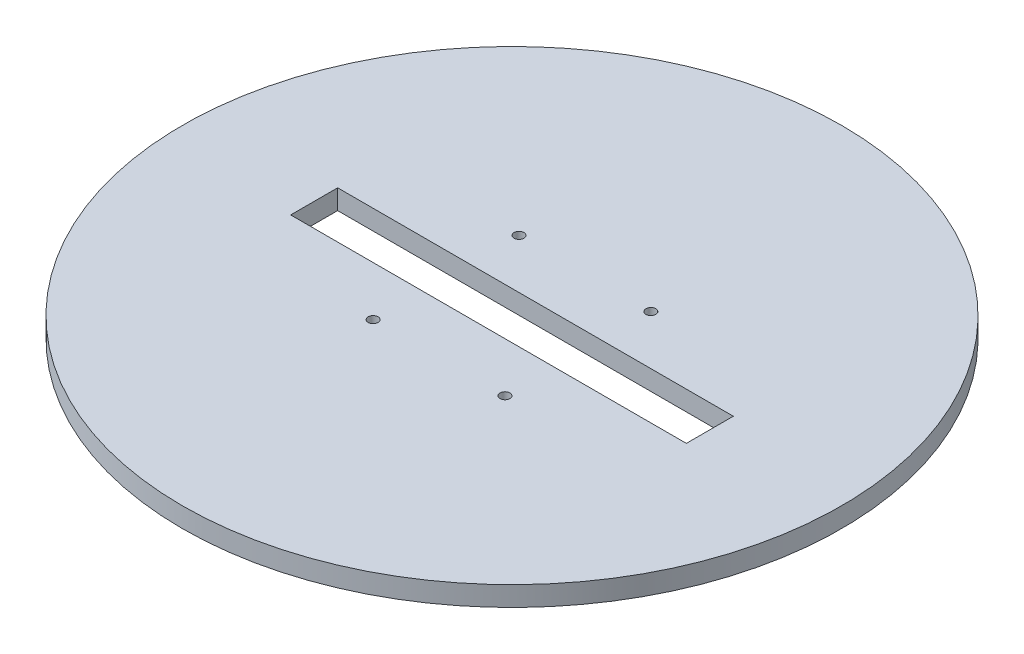
SolidWorks part; units mm, degrees
note: '?' marks a value the reader was unsure of.
ref_plane "Front Plane" through (0, 0, 0) normal (0, 0, 1) x (1, 0, 0)
ref_plane "Top Plane" through (0, 0, 0) normal (0, 1, 0) x (1, 0, 0)
ref_plane "Right Plane" through (0, 0, 0) normal (1, 0, 0) x (0, 0, -1)
sketch "Sketch1" plane through (0, 0, 0) normal (0, 1, 0) x (1, 0, 0)
  line L1 (-60, -7.125) -> (60, -7.125)
  line L2 (-60, -7.125) -> (-60, 7.125)
  line L3 (-60, 7.125) -> (60, 7.125)
  line L4 (60, -7.125) -> (60, 7.125)
  line L5 (-60, -7.125) -> (60, 7.125) construction
  line L6 (-60, 7.125) -> (60, -7.125) construction
  circle A0 centre (0, 0) radius 99.95
extrude "Boss-Extrude1" add sketch "Sketch1" along normal blind 6 contours A0 L4 L1 L2 L3
sketch "Sketch2" plane through (0, 6, 0) normal (0, 1, 0) x (1, 0, 0)
  line L0 (0, 70) -> (0, 80)
  line L1 (1.2217, 69.9893) -> (1.3962, 79.9878)
  line L2 (2.443, 69.9574) -> (2.792, 79.9513)
  line L3 (3.6635, 69.9041) -> (4.1869, 79.8904)
  line L4 (4.883, 69.8295) -> (5.5805, 79.8051)
  line L5 (6.1009, 69.7336) -> (6.9725, 79.6956)
  line L6 (7.317, 69.6165) -> (8.3623, 79.5618)
  line L7 (8.5309, 69.4782) -> (9.7495, 79.4037)
  line L8 (9.7421, 69.3188) -> (11.1338, 79.2214)
  line L9 (10.9504, 69.1382) -> (12.5148, 79.0151)
  line L10 (12.1554, 68.9365) -> (13.8919, 78.7846)
  line L11 (13.3566, 68.7139) -> (15.2647, 78.5302)
  line L12 (14.5538, 68.4703) -> (16.6329, 78.2518)
  line L13 (15.7466, 68.2059) -> (17.9961, 77.9496)
  line L14 (16.9345, 67.9207) -> (19.3538, 77.6237)
  line L15 (18.1173, 67.6148) -> (20.7055, 77.2741)
  line L16 (19.2946, 67.2883) -> (22.051, 76.9009)
  line L17 (20.466, 66.9413) -> (23.3897, 76.5044)
  line L18 (21.6312, 66.574) -> (24.7214, 76.0845)
  line L19 (22.7898, 66.1863) -> (26.0455, 75.6415)
  line L20 (23.9414, 65.7785) -> (27.3616, 75.1754)
  line L21 (25.0858, 65.3506) -> (28.6694, 74.6864)
  line L22 (26.2225, 64.9029) -> (29.9685, 74.1747)
  line L23 (27.3512, 64.4353) -> (31.2585, 73.6404)
  line L24 (28.4716, 63.9482) -> (32.5389, 73.0836)
  line L25 (29.5833, 63.4415) -> (33.8095, 72.5046)
  line L26 (30.686, 62.9156) -> (35.0697, 71.9035)
  line L27 (31.7793, 62.3705) -> (36.3192, 71.2805)
  line L28 (32.863, 61.8063) -> (37.5577, 70.6358)
  line L29 (33.9367, 61.2234) -> (38.7848, 69.9696)
  line L30 (35, 60.6218) -> (40, 69.282)
  line L31 (36.0527, 60.0017) -> (41.203, 68.5734)
  line L32 (37.0943, 59.3634) -> (42.3935, 67.8438)
  line L33 (38.1247, 58.7069) -> (43.5711, 67.0936)
  line L34 (39.1435, 58.0326) -> (44.7354, 66.323)
  line L35 (40.1504, 57.3406) -> (45.8861, 65.5322)
  line L36 (41.145, 56.6312) -> (47.0228, 64.7214)
  line L37 (42.1271, 55.9045) -> (48.1452, 63.8908)
  line L38 (43.0963, 55.1608) -> (49.2529, 63.0409)
  line L39 (44.0524, 54.4002) -> (50.3456, 62.1717)
  line L40 (44.9951, 53.6231) -> (51.423, 61.2836)
  line L41 (45.9241, 52.8297) -> (52.4847, 60.3768)
  line L42 (46.8391, 52.0201) -> (53.5304, 59.4516)
  line L43 (47.7399, 51.1948) -> (54.5599, 58.5083)
  line L44 (48.6261, 50.3538) -> (55.5727, 57.5472)
  line L45 (49.4975, 49.4975) -> (56.5685, 56.5685)
  line L46 (50.3538, 48.6261) -> (57.5472, 55.5727)
  line L47 (51.1948, 47.7399) -> (58.5083, 54.5599)
  line L48 (52.0201, 46.8391) -> (59.4516, 53.5304)
  line L49 (52.8297, 45.9241) -> (60.3768, 52.4847)
  line L50 (53.6231, 44.9951) -> (61.2836, 51.423)
  line L51 (54.4002, 44.0524) -> (62.1717, 50.3456)
  line L52 (55.1608, 43.0963) -> (63.0409, 49.2529)
  line L53 (55.9045, 42.1271) -> (63.8908, 48.1452)
  line L54 (56.6312, 41.145) -> (64.7214, 47.0228)
  line L55 (57.3406, 40.1504) -> (65.5322, 45.8861)
  line L56 (58.0326, 39.1435) -> (66.323, 44.7354)
  line L57 (58.7069, 38.1247) -> (67.0936, 43.5711)
  line L58 (59.3634, 37.0943) -> (67.8438, 42.3935)
  line L59 (60.0017, 36.0527) -> (68.5734, 41.203)
  line L60 (60.6218, 35) -> (69.282, 40)
  line L61 (61.2234, 33.9367) -> (69.9696, 38.7848)
  line L62 (61.8063, 32.863) -> (70.6358, 37.5577)
  line L63 (62.3705, 31.7793) -> (71.2805, 36.3192)
  line L64 (62.9156, 30.686) -> (71.9035, 35.0697)
  line L65 (63.4415, 29.5833) -> (72.5046, 33.8095)
  line L66 (63.9482, 28.4716) -> (73.0836, 32.5389)
  line L67 (64.4353, 27.3512) -> (73.6404, 31.2585)
  line L68 (64.9029, 26.2225) -> (74.1747, 29.9685)
  line L69 (65.3506, 25.0858) -> (74.6864, 28.6694)
  line L70 (65.7785, 23.9414) -> (75.1754, 27.3616)
  line L71 (66.1863, 22.7898) -> (75.6415, 26.0455)
  line L72 (66.574, 21.6312) -> (76.0845, 24.7214)
  line L73 (66.9413, 20.466) -> (76.5044, 23.3897)
  line L74 (67.2883, 19.2946) -> (76.9009, 22.051)
  line L75 (67.6148, 18.1173) -> (77.2741, 20.7055)
  line L76 (67.9207, 16.9345) -> (77.6237, 19.3538)
  line L77 (68.2059, 15.7466) -> (77.9496, 17.9961)
  line L78 (68.4703, 14.5538) -> (78.2518, 16.6329)
  line L79 (68.7139, 13.3566) -> (78.5302, 15.2647)
  line L80 (68.9365, 12.1554) -> (78.7846, 13.8919)
  line L81 (69.1382, 10.9504) -> (79.0151, 12.5148)
  line L82 (69.3188, 9.7421) -> (79.2214, 11.1338)
  line L83 (69.4782, 8.5309) -> (79.4037, 9.7495)
  line L84 (69.6165, 7.317) -> (79.5618, 8.3623)
  line L85 (69.7336, 6.1009) -> (79.6956, 6.9725)
  line L86 (69.8295, 4.883) -> (79.8051, 5.5805)
  line L87 (69.9041, 3.6635) -> (79.8904, 4.1869)
  line L88 (69.9574, 2.443) -> (79.9513, 2.792)
  line L89 (69.9893, 1.2217) -> (79.9878, 1.3962)
  line L90 (70, 0) -> (80, 0)
  line L91 (69.9893, -1.2217) -> (79.9878, -1.3962)
  line L92 (69.9574, -2.443) -> (79.9513, -2.792)
  line L93 (69.9041, -3.6635) -> (79.8904, -4.1869)
  line L94 (69.8295, -4.883) -> (79.8051, -5.5805)
  line L95 (69.7336, -6.1009) -> (79.6956, -6.9725)
  line L96 (69.6165, -7.317) -> (79.5618, -8.3623)
  line L97 (69.4782, -8.5309) -> (79.4037, -9.7495)
  line L98 (69.3188, -9.7421) -> (79.2214, -11.1338)
  line L99 (69.1382, -10.9504) -> (79.0151, -12.5148)
  line L100 (68.9365, -12.1554) -> (78.7846, -13.8919)
  line L101 (68.7139, -13.3566) -> (78.5302, -15.2647)
  line L102 (68.4703, -14.5538) -> (78.2518, -16.6329)
  line L103 (68.2059, -15.7466) -> (77.9496, -17.9961)
  line L104 (67.9207, -16.9345) -> (77.6237, -19.3538)
  line L105 (67.6148, -18.1173) -> (77.2741, -20.7055)
  line L106 (67.2883, -19.2946) -> (76.9009, -22.051)
  line L107 (66.9413, -20.466) -> (76.5044, -23.3897)
  line L108 (66.574, -21.6312) -> (76.0845, -24.7214)
  line L109 (66.1863, -22.7898) -> (75.6415, -26.0455)
  line L110 (65.7785, -23.9414) -> (75.1754, -27.3616)
  line L111 (65.3506, -25.0858) -> (74.6864, -28.6694)
  line L112 (64.9029, -26.2225) -> (74.1747, -29.9685)
  line L113 (64.4353, -27.3512) -> (73.6404, -31.2585)
  line L114 (63.9482, -28.4716) -> (73.0836, -32.5389)
  line L115 (63.4415, -29.5833) -> (72.5046, -33.8095)
  line L116 (62.9156, -30.686) -> (71.9035, -35.0697)
  line L117 (62.3705, -31.7793) -> (71.2805, -36.3192)
  line L118 (61.8063, -32.863) -> (70.6358, -37.5577)
  line L119 (61.2234, -33.9367) -> (69.9696, -38.7848)
  line L120 (60.6218, -35) -> (69.282, -40)
  line L121 (60.0017, -36.0527) -> (68.5734, -41.203)
  line L122 (59.3634, -37.0943) -> (67.8438, -42.3935)
  line L123 (58.7069, -38.1247) -> (67.0936, -43.5711)
  line L124 (58.0326, -39.1435) -> (66.323, -44.7354)
  line L125 (57.3406, -40.1504) -> (65.5322, -45.8861)
  line L126 (56.6312, -41.145) -> (64.7214, -47.0228)
  line L127 (55.9045, -42.1271) -> (63.8908, -48.1452)
  line L128 (55.1608, -43.0963) -> (63.0409, -49.2529)
  line L129 (54.4002, -44.0524) -> (62.1717, -50.3456)
  line L130 (53.6231, -44.9951) -> (61.2836, -51.423)
  line L131 (52.8297, -45.9241) -> (60.3768, -52.4847)
  line L132 (52.0201, -46.8391) -> (59.4516, -53.5304)
  line L133 (51.1948, -47.7399) -> (58.5083, -54.5599)
  line L134 (50.3538, -48.6261) -> (57.5472, -55.5727)
  line L135 (49.4975, -49.4975) -> (56.5685, -56.5685)
  line L136 (48.6261, -50.3538) -> (55.5727, -57.5472)
  line L137 (47.7399, -51.1948) -> (54.5599, -58.5083)
  line L138 (46.8391, -52.0201) -> (53.5304, -59.4516)
  line L139 (45.9241, -52.8297) -> (52.4847, -60.3768)
  line L140 (44.9951, -53.6231) -> (51.423, -61.2836)
  line L141 (44.0524, -54.4002) -> (50.3456, -62.1717)
  line L142 (43.0963, -55.1608) -> (49.2529, -63.0409)
  line L143 (42.1271, -55.9045) -> (48.1452, -63.8908)
  line L144 (41.145, -56.6312) -> (47.0228, -64.7214)
  line L145 (40.1504, -57.3406) -> (45.8861, -65.5322)
  line L146 (39.1435, -58.0326) -> (44.7354, -66.323)
  line L147 (38.1247, -58.7069) -> (43.5711, -67.0936)
  line L148 (37.0943, -59.3634) -> (42.3935, -67.8438)
  line L149 (36.0527, -60.0017) -> (41.203, -68.5734)
  line L150 (35, -60.6218) -> (40, -69.282)
  line L151 (33.9367, -61.2234) -> (38.7848, -69.9696)
  line L152 (32.863, -61.8063) -> (37.5577, -70.6358)
  line L153 (31.7793, -62.3705) -> (36.3192, -71.2805)
  line L154 (30.686, -62.9156) -> (35.0697, -71.9035)
  line L155 (29.5833, -63.4415) -> (33.8095, -72.5046)
  line L156 (28.4716, -63.9482) -> (32.5389, -73.0836)
  line L157 (27.3512, -64.4353) -> (31.2585, -73.6404)
  line L158 (26.2225, -64.9029) -> (29.9685, -74.1747)
  line L159 (25.0858, -65.3506) -> (28.6694, -74.6864)
  line L160 (23.9414, -65.7785) -> (27.3616, -75.1754)
  line L161 (22.7898, -66.1863) -> (26.0455, -75.6415)
  line L162 (21.6312, -66.574) -> (24.7214, -76.0845)
  line L163 (20.466, -66.9413) -> (23.3897, -76.5044)
  line L164 (19.2946, -67.2883) -> (22.051, -76.9009)
  line L165 (18.1173, -67.6148) -> (20.7055, -77.2741)
  line L166 (16.9345, -67.9207) -> (19.3538, -77.6237)
  line L167 (15.7466, -68.2059) -> (17.9961, -77.9496)
  line L168 (14.5538, -68.4703) -> (16.6329, -78.2518)
  line L169 (13.3566, -68.7139) -> (15.2647, -78.5302)
  line L170 (12.1554, -68.9365) -> (13.8919, -78.7846)
  line L171 (10.9504, -69.1382) -> (12.5148, -79.0151)
  line L172 (9.7421, -69.3188) -> (11.1338, -79.2214)
  line L173 (8.5309, -69.4782) -> (9.7495, -79.4037)
  line L174 (7.317, -69.6165) -> (8.3623, -79.5618)
  line L175 (6.1009, -69.7336) -> (6.9725, -79.6956)
  line L176 (4.883, -69.8295) -> (5.5805, -79.8051)
  line L177 (3.6635, -69.9041) -> (4.1869, -79.8904)
  line L178 (2.443, -69.9574) -> (2.792, -79.9513)
  line L179 (1.2217, -69.9893) -> (1.3962, -79.9878)
  line L180 (0, -70) -> (0, -80)
  line L181 (-1.2217, -69.9893) -> (-1.3962, -79.9878)
  line L182 (-2.443, -69.9574) -> (-2.792, -79.9513)
  line L183 (-3.6635, -69.9041) -> (-4.1869, -79.8904)
  line L184 (-4.883, -69.8295) -> (-5.5805, -79.8051)
  line L185 (-6.1009, -69.7336) -> (-6.9725, -79.6956)
  line L186 (-7.317, -69.6165) -> (-8.3623, -79.5618)
  line L187 (-8.5309, -69.4782) -> (-9.7495, -79.4037)
  line L188 (-9.7421, -69.3188) -> (-11.1338, -79.2214)
  line L189 (-10.9504, -69.1382) -> (-12.5148, -79.0151)
  line L190 (-12.1554, -68.9365) -> (-13.8919, -78.7846)
  line L191 (-13.3566, -68.7139) -> (-15.2647, -78.5302)
  line L192 (-14.5538, -68.4703) -> (-16.6329, -78.2518)
  line L193 (-15.7466, -68.2059) -> (-17.9961, -77.9496)
  line L194 (-16.9345, -67.9207) -> (-19.3538, -77.6237)
  line L195 (-18.1173, -67.6148) -> (-20.7055, -77.2741)
  line L196 (-19.2946, -67.2883) -> (-22.051, -76.9009)
  line L197 (-20.466, -66.9413) -> (-23.3897, -76.5044)
  line L198 (-21.6312, -66.574) -> (-24.7214, -76.0845)
  line L199 (-22.7898, -66.1863) -> (-26.0455, -75.6415)
  line L200 (-23.9414, -65.7785) -> (-27.3616, -75.1754)
  line L201 (-25.0858, -65.3506) -> (-28.6694, -74.6864)
  line L202 (-26.2225, -64.9029) -> (-29.9685, -74.1747)
  line L203 (-27.3512, -64.4353) -> (-31.2585, -73.6404)
  line L204 (-28.4716, -63.9482) -> (-32.5389, -73.0836)
  line L205 (-29.5833, -63.4415) -> (-33.8095, -72.5046)
  line L206 (-30.686, -62.9156) -> (-35.0697, -71.9035)
  line L207 (-31.7793, -62.3705) -> (-36.3192, -71.2805)
  line L208 (-32.863, -61.8063) -> (-37.5577, -70.6358)
  line L209 (-33.9367, -61.2234) -> (-38.7848, -69.9696)
  line L210 (-35, -60.6218) -> (-40, -69.282)
  line L211 (-36.0527, -60.0017) -> (-41.203, -68.5734)
  line L212 (-37.0943, -59.3634) -> (-42.3935, -67.8438)
  line L213 (-38.1247, -58.7069) -> (-43.5711, -67.0936)
  line L214 (-39.1435, -58.0326) -> (-44.7354, -66.323)
  line L215 (-40.1504, -57.3406) -> (-45.8861, -65.5322)
  line L216 (-41.145, -56.6312) -> (-47.0228, -64.7214)
  line L217 (-42.1271, -55.9045) -> (-48.1452, -63.8908)
  line L218 (-43.0963, -55.1608) -> (-49.2529, -63.0409)
  line L219 (-44.0524, -54.4002) -> (-50.3456, -62.1717)
  line L220 (-44.9951, -53.6231) -> (-51.423, -61.2836)
  line L221 (-45.9241, -52.8297) -> (-52.4847, -60.3768)
  line L222 (-46.8391, -52.0201) -> (-53.5304, -59.4516)
  line L223 (-47.7399, -51.1948) -> (-54.5599, -58.5083)
  line L224 (-48.6261, -50.3538) -> (-55.5727, -57.5472)
  line L225 (-49.4975, -49.4975) -> (-56.5685, -56.5685)
  line L226 (-50.3538, -48.6261) -> (-57.5472, -55.5727)
  line L227 (-51.1948, -47.7399) -> (-58.5083, -54.5599)
  line L228 (-52.0201, -46.8391) -> (-59.4516, -53.5304)
  line L229 (-52.8297, -45.9241) -> (-60.3768, -52.4847)
  line L230 (-53.6231, -44.9951) -> (-61.2836, -51.423)
  line L231 (-54.4002, -44.0524) -> (-62.1717, -50.3456)
  line L232 (-55.1608, -43.0963) -> (-63.0409, -49.2529)
  line L233 (-55.9045, -42.1271) -> (-63.8908, -48.1452)
  line L234 (-56.6312, -41.145) -> (-64.7214, -47.0228)
  line L235 (-57.3406, -40.1504) -> (-65.5322, -45.8861)
  line L236 (-58.0326, -39.1435) -> (-66.323, -44.7354)
  line L237 (-58.7069, -38.1247) -> (-67.0936, -43.5711)
  line L238 (-59.3634, -37.0943) -> (-67.8438, -42.3935)
  line L239 (-60.0017, -36.0527) -> (-68.5734, -41.203)
  line L240 (-60.6218, -35) -> (-69.282, -40)
  line L241 (-61.2234, -33.9367) -> (-69.9696, -38.7848)
  line L242 (-61.8063, -32.863) -> (-70.6358, -37.5577)
  line L243 (-62.3705, -31.7793) -> (-71.2805, -36.3192)
  line L244 (-62.9156, -30.686) -> (-71.9035, -35.0697)
  line L245 (-63.4415, -29.5833) -> (-72.5046, -33.8095)
  line L246 (-63.9482, -28.4716) -> (-73.0836, -32.5389)
  line L247 (-64.4353, -27.3512) -> (-73.6404, -31.2585)
  line L248 (-64.9029, -26.2225) -> (-74.1747, -29.9685)
  line L249 (-65.3506, -25.0858) -> (-74.6864, -28.6694)
  line L250 (-65.7785, -23.9414) -> (-75.1754, -27.3616)
  line L251 (-66.1863, -22.7898) -> (-75.6415, -26.0455)
  line L252 (-66.574, -21.6312) -> (-76.0845, -24.7214)
  line L253 (-66.9413, -20.466) -> (-76.5044, -23.3897)
  line L254 (-67.2883, -19.2946) -> (-76.9009, -22.051)
  line L255 (-67.6148, -18.1173) -> (-77.2741, -20.7055)
  line L256 (-67.9207, -16.9345) -> (-77.6237, -19.3538)
  line L257 (-68.2059, -15.7466) -> (-77.9496, -17.9961)
  line L258 (-68.4703, -14.5538) -> (-78.2518, -16.6329)
  line L259 (-68.7139, -13.3566) -> (-78.5302, -15.2647)
  line L260 (-68.9365, -12.1554) -> (-78.7846, -13.8919)
  line L261 (-69.1382, -10.9504) -> (-79.0151, -12.5148)
  line L262 (-69.3188, -9.7421) -> (-79.2214, -11.1338)
  line L263 (-69.4782, -8.5309) -> (-79.4037, -9.7495)
  line L264 (-69.6165, -7.317) -> (-79.5618, -8.3623)
  line L265 (-69.7336, -6.1009) -> (-79.6956, -6.9725)
  line L266 (-69.8295, -4.883) -> (-79.8051, -5.5805)
  line L267 (-69.9041, -3.6635) -> (-79.8904, -4.1869)
  line L268 (-69.9574, -2.443) -> (-79.9513, -2.792)
  line L269 (-69.9893, -1.2217) -> (-79.9878, -1.3962)
  line L270 (-70, 0) -> (-80, 0)
  line L271 (-69.9893, 1.2217) -> (-79.9878, 1.3962)
  line L272 (-69.9574, 2.443) -> (-79.9513, 2.792)
  line L273 (-69.9041, 3.6635) -> (-79.8904, 4.1869)
  line L274 (-69.8295, 4.883) -> (-79.8051, 5.5805)
  line L275 (-69.7336, 6.1009) -> (-79.6956, 6.9725)
  line L276 (-69.6165, 7.317) -> (-79.5618, 8.3623)
  line L277 (-69.4782, 8.5309) -> (-79.4037, 9.7495)
  line L278 (-69.3188, 9.7421) -> (-79.2214, 11.1338)
  line L279 (-69.1382, 10.9504) -> (-79.0151, 12.5148)
  line L280 (-68.9365, 12.1554) -> (-78.7846, 13.8919)
  line L281 (-68.7139, 13.3566) -> (-78.5302, 15.2647)
  line L282 (-68.4703, 14.5538) -> (-78.2518, 16.6329)
  line L283 (-68.2059, 15.7466) -> (-77.9496, 17.9961)
  line L284 (-67.9207, 16.9345) -> (-77.6237, 19.3538)
  line L285 (-67.6148, 18.1173) -> (-77.2741, 20.7055)
  line L286 (-67.2883, 19.2946) -> (-76.9009, 22.051)
  line L287 (-66.9413, 20.466) -> (-76.5044, 23.3897)
  line L288 (-66.574, 21.6312) -> (-76.0845, 24.7214)
  line L289 (-66.1863, 22.7898) -> (-75.6415, 26.0455)
  line L290 (-65.7785, 23.9414) -> (-75.1754, 27.3616)
  line L291 (-65.3506, 25.0858) -> (-74.6864, 28.6694)
  line L292 (-64.9029, 26.2225) -> (-74.1747, 29.9685)
  line L293 (-64.4353, 27.3512) -> (-73.6404, 31.2585)
  line L294 (-63.9482, 28.4716) -> (-73.0836, 32.5389)
  line L295 (-63.4415, 29.5833) -> (-72.5046, 33.8095)
  line L296 (-62.9156, 30.686) -> (-71.9035, 35.0697)
  line L297 (-62.3705, 31.7793) -> (-71.2805, 36.3192)
  line L298 (-61.8063, 32.863) -> (-70.6358, 37.5577)
  line L299 (-61.2234, 33.9367) -> (-69.9696, 38.7848)
  line L300 (-60.6218, 35) -> (-69.282, 40)
  line L301 (-60.0017, 36.0527) -> (-68.5734, 41.203)
  line L302 (-59.3634, 37.0943) -> (-67.8438, 42.3935)
  line L303 (-58.7069, 38.1247) -> (-67.0936, 43.5711)
  line L304 (-58.0326, 39.1435) -> (-66.323, 44.7354)
  line L305 (-57.3406, 40.1504) -> (-65.5322, 45.8861)
  line L306 (-56.6312, 41.145) -> (-64.7214, 47.0228)
  line L307 (-55.9045, 42.1271) -> (-63.8908, 48.1452)
  line L308 (-55.1608, 43.0963) -> (-63.0409, 49.2529)
  line L309 (-54.4002, 44.0524) -> (-62.1717, 50.3456)
  line L310 (-53.6231, 44.9951) -> (-61.2836, 51.423)
  line L311 (-52.8297, 45.9241) -> (-60.3768, 52.4847)
  line L312 (-52.0201, 46.8391) -> (-59.4516, 53.5304)
  line L313 (-51.1948, 47.7399) -> (-58.5083, 54.5599)
  line L314 (-50.3538, 48.6261) -> (-57.5472, 55.5727)
  line L315 (-49.4975, 49.4975) -> (-56.5685, 56.5685)
  line L316 (-48.6261, 50.3538) -> (-55.5727, 57.5472)
  line L317 (-47.7399, 51.1948) -> (-54.5599, 58.5083)
  line L318 (-46.8391, 52.0201) -> (-53.5304, 59.4516)
  line L319 (-45.9241, 52.8297) -> (-52.4847, 60.3768)
  line L320 (-44.9951, 53.6231) -> (-51.423, 61.2836)
  line L321 (-44.0524, 54.4002) -> (-50.3456, 62.1717)
  line L322 (-43.0963, 55.1608) -> (-49.2529, 63.0409)
  line L323 (-42.1271, 55.9045) -> (-48.1452, 63.8908)
  line L324 (-41.145, 56.6312) -> (-47.0228, 64.7214)
  line L325 (-40.1504, 57.3406) -> (-45.8861, 65.5322)
  line L326 (-39.1435, 58.0326) -> (-44.7354, 66.323)
  line L327 (-38.1247, 58.7069) -> (-43.5711, 67.0936)
  line L328 (-37.0943, 59.3634) -> (-42.3935, 67.8438)
  line L329 (-36.0527, 60.0017) -> (-41.203, 68.5734)
  line L330 (-35, 60.6218) -> (-40, 69.282)
  line L331 (-33.9367, 61.2234) -> (-38.7848, 69.9696)
  line L332 (-32.863, 61.8063) -> (-37.5577, 70.6358)
  line L333 (-31.7793, 62.3705) -> (-36.3192, 71.2805)
  line L334 (-30.686, 62.9156) -> (-35.0697, 71.9035)
  line L335 (-29.5833, 63.4415) -> (-33.8095, 72.5046)
  line L336 (-28.4716, 63.9482) -> (-32.5389, 73.0836)
  line L337 (-27.3512, 64.4353) -> (-31.2585, 73.6404)
  line L338 (-26.2225, 64.9029) -> (-29.9685, 74.1747)
  line L339 (-25.0858, 65.3506) -> (-28.6694, 74.6864)
  line L340 (-23.9414, 65.7785) -> (-27.3616, 75.1754)
  line L341 (-22.7898, 66.1863) -> (-26.0455, 75.6415)
  line L342 (-21.6312, 66.574) -> (-24.7214, 76.0845)
  line L343 (-20.466, 66.9413) -> (-23.3897, 76.5044)
  line L344 (-19.2946, 67.2883) -> (-22.051, 76.9009)
  line L345 (-18.1173, 67.6148) -> (-20.7055, 77.2741)
  line L346 (-16.9345, 67.9207) -> (-19.3538, 77.6237)
  line L347 (-15.7466, 68.2059) -> (-17.9961, 77.9496)
  line L348 (-14.5538, 68.4703) -> (-16.6329, 78.2518)
  line L349 (-13.3566, 68.7139) -> (-15.2647, 78.5302)
  line L350 (-12.1554, 68.9365) -> (-13.8919, 78.7846)
  line L351 (-10.9504, 69.1382) -> (-12.5148, 79.0151)
  line L352 (-9.7421, 69.3188) -> (-11.1338, 79.2214)
  line L353 (-8.5309, 69.4782) -> (-9.7495, 79.4037)
  line L354 (-7.317, 69.6165) -> (-8.3623, 79.5618)
  line L355 (-6.1009, 69.7336) -> (-6.9725, 79.6956)
  line L356 (-4.883, 69.8295) -> (-5.5805, 79.8051)
  line L357 (-3.6635, 69.9041) -> (-4.1869, 79.8904)
  line L358 (-2.443, 69.9574) -> (-2.792, 79.9513)
  line L359 (-1.2217, 69.9893) -> (-1.3962, 79.9878)
  line L360 (0, 80) -> (0, 82.5)
  line L361 (6.9725, 79.6956) -> (7.1903, 82.1861)
  line L362 (13.8919, 78.7846) -> (14.326, 81.2466)
  line L363 (20.7055, 77.2741) -> (21.3526, 79.6889)
  line L364 (27.3616, 75.1754) -> (28.2167, 77.5246)
  line L365 (33.8095, 72.5046) -> (34.866, 74.7704)
  line L366 (40, 69.282) -> (41.25, 71.4471)
  line L367 (45.8861, 65.5322) -> (47.3201, 67.58)
  line L368 (51.423, 61.2836) -> (53.03, 63.1987)
  line L369 (56.5685, 56.5685) -> (58.3363, 58.3363)
  line L370 (61.2836, 51.423) -> (63.1987, 53.03)
  line L371 (65.5322, 45.8861) -> (67.58, 47.3201)
  line L372 (69.282, 40) -> (71.4471, 41.25)
  line L373 (72.5046, 33.8095) -> (74.7704, 34.866)
  line L374 (75.1754, 27.3616) -> (77.5246, 28.2167)
  line L375 (77.2741, 20.7055) -> (79.6889, 21.3526)
  line L376 (78.7846, 13.8919) -> (81.2466, 14.326)
  line L377 (79.6956, 6.9725) -> (82.1861, 7.1903)
  line L378 (80, 0) -> (82.5, 0)
  line L379 (79.6956, -6.9725) -> (82.1861, -7.1903)
  line L380 (78.7846, -13.8919) -> (81.2466, -14.326)
  line L381 (77.2741, -20.7055) -> (79.6889, -21.3526)
  line L382 (75.1754, -27.3616) -> (77.5246, -28.2167)
  line L383 (72.5046, -33.8095) -> (74.7704, -34.866)
  line L384 (69.282, -40) -> (71.4471, -41.25)
  line L385 (65.5322, -45.8861) -> (67.58, -47.3201)
  line L386 (61.2836, -51.423) -> (63.1987, -53.03)
  line L387 (56.5685, -56.5685) -> (58.3363, -58.3363)
  line L388 (51.423, -61.2836) -> (53.03, -63.1987)
  line L389 (45.8861, -65.5322) -> (47.3201, -67.58)
  line L390 (40, -69.282) -> (41.25, -71.4471)
  line L391 (33.8095, -72.5046) -> (34.866, -74.7704)
  line L392 (27.3616, -75.1754) -> (28.2167, -77.5246)
  line L393 (20.7055, -77.2741) -> (21.3526, -79.6889)
  line L394 (13.8919, -78.7846) -> (14.326, -81.2466)
  line L395 (6.9725, -79.6956) -> (7.1903, -82.1861)
  line L396 (0, -80) -> (0, -82.5)
  line L397 (-6.9725, -79.6956) -> (-7.1903, -82.1861)
  line L398 (-13.8919, -78.7846) -> (-14.326, -81.2466)
  line L399 (-20.7055, -77.2741) -> (-21.3526, -79.6889)
  line L400 (-27.3616, -75.1754) -> (-28.2167, -77.5246)
  line L401 (-33.8095, -72.5046) -> (-34.866, -74.7704)
  line L402 (-40, -69.282) -> (-41.25, -71.4471)
  line L403 (-45.8861, -65.5322) -> (-47.3201, -67.58)
  line L404 (-51.423, -61.2836) -> (-53.03, -63.1987)
  line L405 (-56.5685, -56.5685) -> (-58.3363, -58.3363)
  line L406 (-61.2836, -51.423) -> (-63.1987, -53.03)
  line L407 (-65.5322, -45.8861) -> (-67.58, -47.3201)
  line L408 (-69.282, -40) -> (-71.4471, -41.25)
  line L409 (-72.5046, -33.8095) -> (-74.7704, -34.866)
  line L410 (-75.1754, -27.3616) -> (-77.5246, -28.2167)
  line L411 (-77.2741, -20.7055) -> (-79.6889, -21.3526)
  line L412 (-78.7846, -13.8919) -> (-81.2466, -14.326)
  line L413 (-79.6956, -6.9725) -> (-82.1861, -7.1903)
  line L414 (-80, 0) -> (-82.5, 0)
  line L415 (-79.6956, 6.9725) -> (-82.1861, 7.1903)
  line L416 (-78.7846, 13.8919) -> (-81.2466, 14.326)
  line L417 (-77.2741, 20.7055) -> (-79.6889, 21.3526)
  line L418 (-75.1754, 27.3616) -> (-77.5246, 28.2167)
  line L419 (-72.5046, 33.8095) -> (-74.7704, 34.866)
  line L420 (-69.282, 40) -> (-71.4471, 41.25)
  line L421 (-65.5322, 45.8861) -> (-67.58, 47.3201)
  line L422 (-61.2836, 51.423) -> (-63.1987, 53.03)
  line L423 (-56.5685, 56.5685) -> (-58.3363, 58.3363)
  line L424 (-51.423, 61.2836) -> (-53.03, 63.1987)
  line L425 (-45.8861, 65.5322) -> (-47.3201, 67.58)
  line L426 (-40, 69.282) -> (-41.25, 71.4471)
  line L427 (-33.8095, 72.5046) -> (-34.866, 74.7704)
  line L428 (-27.3616, 75.1754) -> (-28.2167, 77.5246)
  line L429 (-20.7055, 77.2741) -> (-21.3526, 79.6889)
  line L430 (-13.8919, 78.7846) -> (-14.326, 81.2466)
  line L431 (-6.9725, 79.6956) -> (-7.1903, 82.1861)
  line L432 (80, -7.5) -> (80, 7.5) construction
  line L433 (-7.5, -80) -> (7.5, -80) construction
  line L434 (-80, 7.5) -> (-80, -7.5) construction
  line L435 (7.5, 80) -> (-7.5, 80) construction
  text T0 "0°"
  text T1 "90°"
  text T2 "180°"
  text T3 "270°"
  point P723 (0, 0)
  point P726 (80, 0)
  point P744 (0, 0)
  point P868 (0, 0)
  dimension "D1" = 70
  dimension "D2" = 10
  dimension "D4" = 80
  dimension "D3" = 360
  dimension "D5" = 4
sketch "Sketch3" plane through (0, 6, 0) normal (0, 1, 0) x (1, 0, 0)
  line L1 (-60, 0) -> (60, 0) construction
  line L2 (-60, -7.125) -> (-60, 7.125) construction
  line L3 (60, -7.125) -> (60, 7.125) construction
  line L4 (0, -41.8739) -> (0, 50.4828) construction
  line L5 (-60, 0) -> (60, 0) construction
  line L6 (-60, -7.125) -> (60, -7.125) construction
  circle A2 centre (-20, -22.125) radius 1.5
  circle A3 centre (20, -22.125) radius 1.5
  circle A4 centre (20, 22.125) radius 1.5
  circle A5 centre (-20, 22.125) radius 1.5
  dimension "D1" = 20
  dimension "D2" = 15
extrude "Cut-Extrude1" cut sketch "Sketch3" against normal through all
convert to sheet metal "Convert-Solid1" [suppressed] bend radius? 10 thickness? 4.75
sketch "Bend-Lines1" [suppressed] plane through (0, 0, 0) normal (0, 1, 0) x (1, 0, 0)
sketch "Bounding-Box1" [suppressed] plane through (0, 0, 0) normal (0, 1, 0) x (1, 0, 0)
sheet metal parameters "Sheet-Metal2" thickness 4.75 parameters "D1"=10
flat pattern "Flat-Pattern2" [suppressed]
sketch "Bend-Lines2" [suppressed] plane through (0, 0, 0) normal (0, 1, 0) x (1, 0, 0)
sketch3d "Bounding-Box2" [suppressed]
  line L0 (-100.0717, 99.828, 0) -> (-99.828, -100.0717, 0) construction
  line L1 (99.828, 100.0717, 0) -> (100.0717, -99.828, 0) construction
  line L2 (-100.0717, 99.828, 0) -> (99.828, 100.0717, 0) construction
  line L3 (-99.828, -100.0717, 0) -> (100.0717, -99.828, 0) construction
